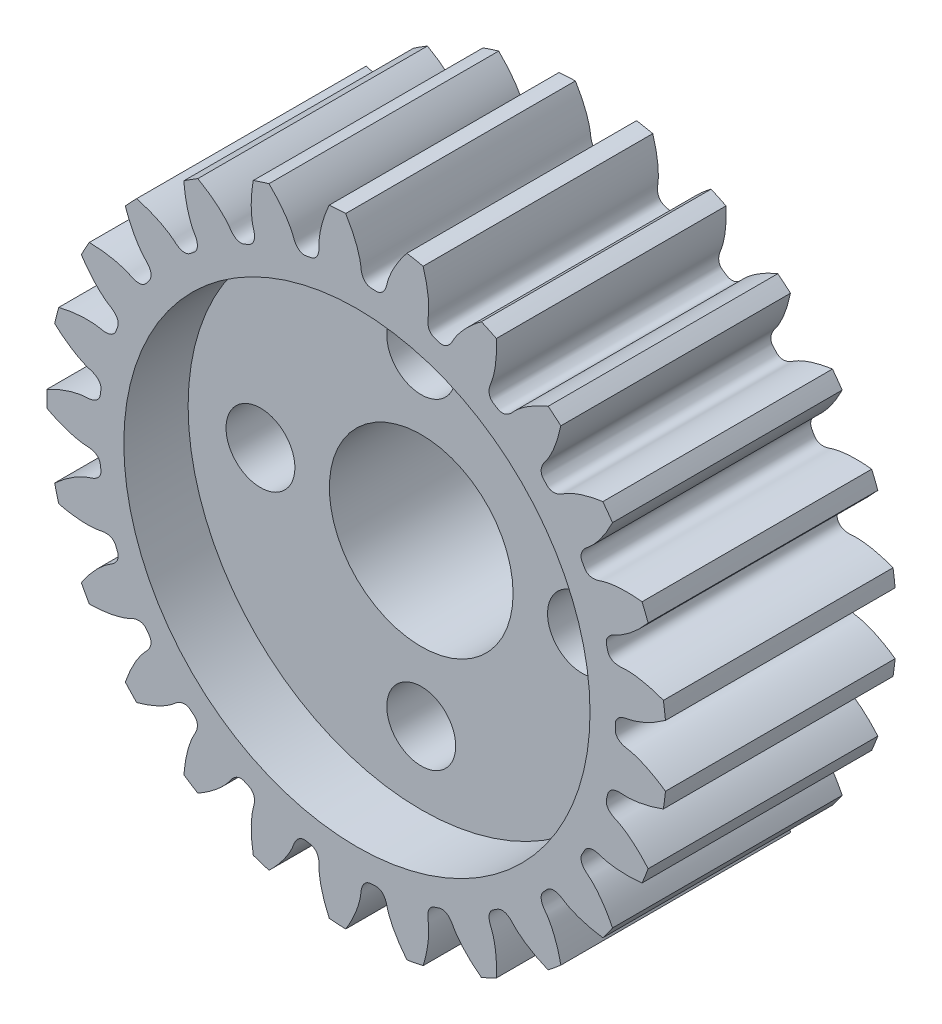
SolidWorks part; units mm, degrees
material "Д16 ГОСТ 4784-97"
ref_plane "FRONT" through (0, 0, 0) normal (0, 0, 1) x (1, 0, 0)
ref_plane "TOP" through (0, 0, 0) normal (0, 1, 0) x (1, 0, 0)
ref_plane "RIGHT" through (0, 0, 0) normal (1, 0, 0) x (0, 0, -1)
ref_axis "Ось1" through (0, 0, 50) along (0, 0, -1)
sketch "SketchRevolveSpurPinion" plane through (0, 0, 0) normal (1, 0, 0) x (0, 0, -1)
  line L0 (0, 0) -> (1, 0) construction
  line L1 (-5, 0) -> (-5, 13.5)
  line L2 (-5, 13.5) -> (5, 13.5)
  line L3 (5, 13.5) -> (5, 0)
  line L4 (5, 0) -> (-5, 0)
revolve "SpurPinion" add sketch "SketchRevolveSpurPinion" angle 360 about L0
sketch "SketchToothSpurPinion" plane through (0, 0, 0) normal (0, 0, 1) x (1, 0, 0)
  arc A0 (13.4808, 1.3678) -> (13.4808, -1.3678) centre (0, 0) cw
  spline S0 degree 3 poles (13.4808, -1.3678) (13.3349, -1.263) (13.1402, -1.1344) (12.8947, -0.993) (12.7622, -0.9216) (12.6363, -0.8584) (12.5175, -0.8029) (12.406, -0.7547) (12.3023, -0.7134) (12.2065, -0.6784) (12.119, -0.6492) (12.0399, -0.6253) (11.9696, -0.6063) (11.9082, -0.5916) (11.8243, -0.5737) (11.7505, -0.5638) (11.6862, -0.549) (11.6589, -0.542) (11.6321, -0.5343) (11.6059, -0.5259) (11.5802, -0.5169) (11.5549, -0.507) (11.5301, -0.4962) (11.5057, -0.4845) (11.4815, -0.4717) (11.4577, -0.4576) (11.4341, -0.4421) (11.4107, -0.4249) (11.3876, -0.4056) (11.3648, -0.3841) (11.3427, -0.3599) (11.3213, -0.3325) (11.3014, -0.3018) (11.2834, -0.2675) (11.2683, -0.2296) (11.2571, -0.1885) (11.2509, -0.1476) (11.2482, -0.0845) (11.2513, 0) (11.2482, 0.0845) (11.2509, 0.1476) (11.2571, 0.1885) (11.2683, 0.2296) (11.2834, 0.2675) (11.3014, 0.3018) (11.3213, 0.3325) (11.3427, 0.3599) (11.3648, 0.3841) (11.3876, 0.4056) (11.4107, 0.4249) (11.4341, 0.4421) (11.4577, 0.4576) (11.4815, 0.4717) (11.5057, 0.4845) (11.5301, 0.4962) (11.5549, 0.507) (11.5802, 0.5169) (11.6059, 0.5259) (11.6321, 0.5343) (11.6589, 0.542) (11.6862, 0.549) (11.7505, 0.5638) (11.8243, 0.5737) (11.9082, 0.5916) (11.9696, 0.6063) (12.0399, 0.6253) (12.119, 0.6492) (12.2065, 0.6784) (12.3023, 0.7134) (12.406, 0.7547) (12.5175, 0.8029) (12.6363, 0.8584) (12.7622, 0.9216) (12.8947, 0.993) (13.1402, 1.1344) (13.3349, 1.263) (13.4808, 1.3678) knots 0 0 0 0 0.097255 0.12617 0.153333 0.178744 0.202402 0.224308 0.244461 0.262862 0.27951 0.294406 0.307549 0.31894 0.328579 0.354008 0.359183 0.364276 0.369295 0.374255 0.379167 0.38405 0.388922 0.393804 0.398723 0.403708 0.408793 0.414017 0.419422 0.425055 0.430965 0.437198 0.443793 0.450772 0.458134 0.46584 0.473813 0.480451 0.5 0.519549 0.526187 0.53416 0.541866 0.549228 0.556207 0.562802 0.569035 0.574945 0.580578 0.585983 0.591207 0.596292 0.601277 0.606196 0.611078 0.61595 0.620833 0.625745 0.630705 0.635724 0.640817 0.645992 0.671421 0.68106 0.692451 0.705594 0.72049 0.737138 0.755539 0.775692 0.797598 0.821256 0.846667 0.87383 0.902745 1 1 1 1
extrude "ToothExtrudeCutSpurPinion" cut sketch "SketchToothSpurPinion" against normal blind 5 and the other way blind 5
pattern_circular "PatternSpurPinion" count 25 every 14.4 about axis through (0, 0, 50) along (0, 0, -1) of "ToothExtrudeCutSpurPinion"
sketch "AuxiliarySketchSpurPinion" plane through (0, 0, 0) normal (0, 0, 1) x (1, 0, 0)
  circle A0 centre (0, 0) radius 12.5 construction
  circle A1 centre (0, 0) radius 11.7462 construction
  circle A2 centre (0, 0) radius 11.8071 construction
  circle A3 centre (0, 0) radius 13.5 construction
  circle A4 centre (0, 0) radius 11.25 construction
  dimension "PitchDiameter" = 25
  dimension "BaseDiameter" = 23.4923
  dimension "FormDiameter" = 23.6141
  dimension "MajorDiameter" = 27
  dimension "MinorDiameter" = 22.5
sketch "Эскиз6" plane through (0, 0, 5) normal (0, 0, 1) x (1, 0, 0)
  circle A0 centre (0, 0) radius 10.15
extrude "Вырез-Вытянуть3" cut sketch "Эскиз6" against normal blind 2.8
sketch "Эскиз5" plane through (0, 0, 5) normal (0, 0, 1) x (1, 0, 0)
  circle A0 centre (0, 0) radius 7 construction
  circle A1 centre (0, 0) radius 8.5 construction
  circle A2 centre (0, 7) radius 1.5
  circle A3 centre (7, 0) radius 1.5
  circle A4 centre (0, -7) radius 1.5
  circle A5 centre (-7, 0) radius 1.5
  circle A6 centre (0, 0) radius 4
  dimension "D1" = 14
  dimension "D2" = 17
  dimension "D3" = 8
extrude "Вырез-Вытянуть2" cut sketch "Эскиз5" against normal through all
